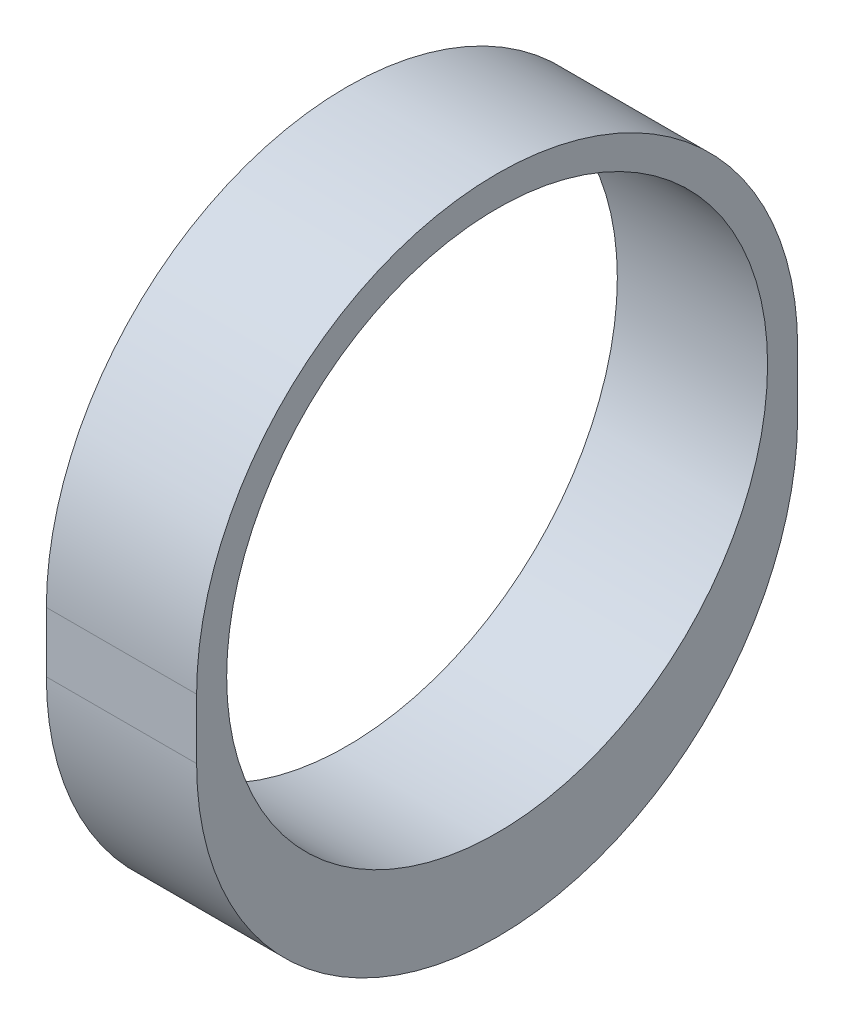
SolidWorks part; units mm, degrees
ref_plane "Piano frontale" through (0, 0, 0) normal (0, 0, 1) x (1, 0, 0)
ref_plane "Piano superiore" through (0, 0, 0) normal (0, 1, 0) x (1, 0, 0)
ref_plane "Piano destro" through (0, 0, 0) normal (1, 0, 0) x (0, 0, -1)
sketch "Schizzo1" plane through (0, 0, 0) normal (1, 0, 0) x (0, 0, -1)
  line L0 (0, -12) -> (0, 10) construction
  line L1 (-10, 0) -> (10, 0) construction
  line L2 (-10, 0) -> (-10, -2)
  line L3 (10, 0) -> (10, -2)
  circle A0 centre (0, 0) radius 9
  arc A1 (10, 0) -> (-10, 0) centre (0, 0) ccw
  arc A2 (-10, -2) -> (10, -2) centre (0, -2) ccw
  point P7 (0, 0)
  point P10 (0, 0)
  dimension "D1" = 18
  dimension "D2" = 10
  dimension "D4" = 10
  dimension "D3" = 2
extrude "Estrusione-Estrusione1" add sketch "Schizzo1" along normal mid plane 5
